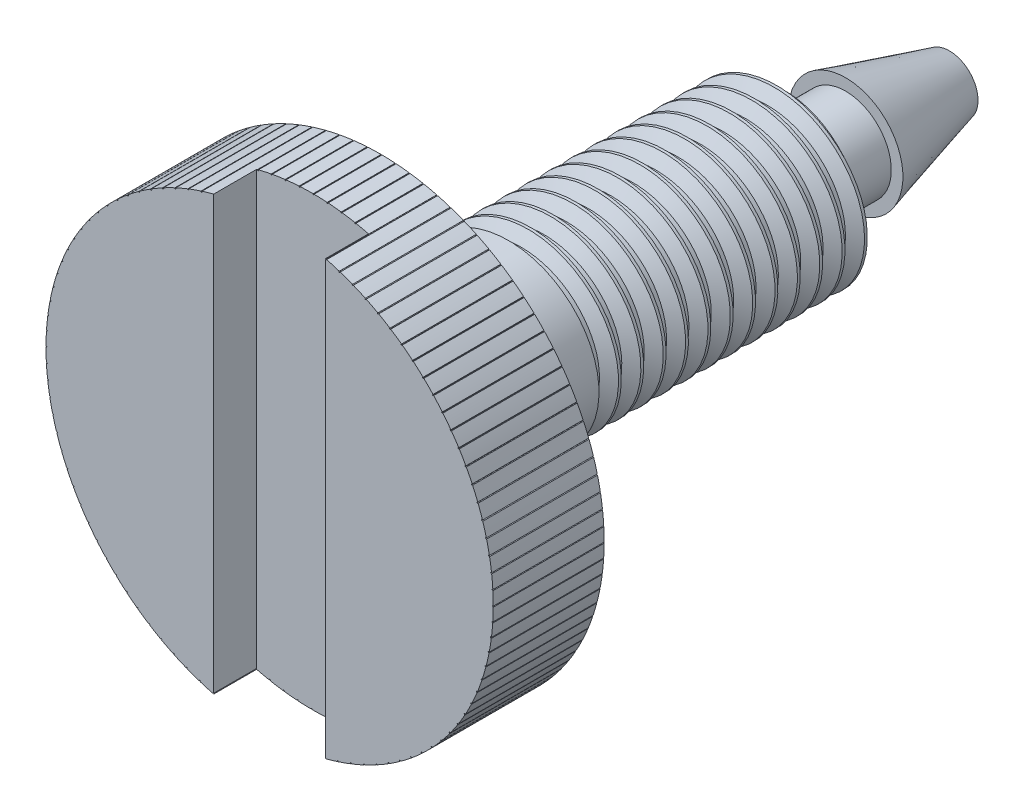
SolidWorks part; units mm, degrees
other "Markup1"
sketch "Sketch10" plane through (-3.175, 3.175, -9.652) normal (-0.9356, 0.3399, -0.0956) x (0.0407, 0.3726, 0.9271)
material "Brass"
ref_plane "Front Plane" through (0, 0, 0) normal (0, 0, 1) x (1, 0, 0)
ref_plane "Top Plane" through (0, 0, 0) normal (0, 1, 0) x (1, 0, 0)
ref_plane "Right Plane" through (0, 0, 0) normal (1, 0, 0) x (0, 0, -1)
sketch "Sketch1" plane through (0, 0, 0) normal (0, 1, 0) x (1, 0, 0)
  line L0 (0, 0) -> (3.175, 0)
  line L1 (3.175, 0) -> (3.175, 1.5748)
  line L2 (3.175, 1.5748) -> (1.2573, 1.5748)
  line L3 (1.2573, 1.5748) -> (1.2573, 7.3152)
  line L4 (1.2573, 7.3152) -> (0.6477, 7.3152)
  line L7 (0, 9.652) -> (0, 0) construction
  line L8 (0, 0) -> (0, 9.652)
  line L10 (0.6477, 7.3152) -> (0.6477, 8.1788)
  line L13 (0.6477, 8.1788) -> (0.8128, 8.1788)
  line L14 (0.8128, 8.1788) -> (0.4064, 9.652)
  line L15 (0, 9.652) -> (0.4064, 9.652)
  dimension "D1" = 3.175
  dimension "D2" = 0.6096
  dimension "D3" = 0.4064
  dimension "D4" = 9.652
  dimension "D5" = 1.5748
  dimension "D6" = 1.2573
  dimension "D7" = 5.7404
  dimension "D8" = 0.8636
  dimension "D9" = 0.1651
revolve "Revolve1" add sketch "Sketch1" angle 360 about L7
cosmetic thread "Cosmetic Thread2" parameters "D2"=1.1455
sketch "Sketch2" plane through (0, 0, 0) normal (0, 1, 0) x (1, 0, 0)
  line L1 (-0.7937, -0.6096) -> (0.7938, -0.6096)
  line L2 (-0.7937, -0.6096) -> (-0.7937, 0.6096)
  line L3 (-0.7937, 0.6096) -> (0.7938, 0.6096)
  line L4 (0.7938, -0.6096) -> (0.7938, 0.6096)
  line L5 (-0.7937, -0.6096) -> (0.7938, 0.6096) construction
  line L6 (-0.7937, 0.6096) -> (0.7938, -0.6096) construction
  point P0 (0, 0)
  dimension "D1" = 1.5875
  dimension "D2" = 1.2192
extrude "Cut-Extrude1" cut sketch "Sketch2" against normal mid plane 12.7
thread "Thread1" pitch 0.3175 method cut profile "Thread Profile1" start angle 0, offset 0.508, length 4.318, pitch 0.3175, diameter 2.5146
cosmetic thread "Cosmetic Thread1" parameters "D2"=1.5146
cosmetic thread "Cosmetic Thread3" parameters "D2"=1.1455
cosmetic thread "Cosmetic Thread4" parameters "D2"=1.1455
ref_plane "Plane1" through (1.2573, 0, -7.8232) normal (0, -1, 0) x (1, 0, 0)
sketch "Thread Profile1" plane through (1.2573, 0, -7.8232) normal (0, -1, 0) x (1, 0, 0)
  line L0 (0, 0) -> (0, 0.3175) construction
  line L11 (0, 0) -> (0, 0.2778)
  line L12 (0, 0.2778) -> (-0.1719, 0.1786)
  line L13 (-0.1719, 0.1786) -> (-0.1719, 0.0992)
  line L15 (-0.1719, 0.0992) -> (0, 0)
  line L17 (-0.1719, 0.1389) -> (0, 0.1389) construction
  point P2 (0, 0)
  dimension "Pitch" = 0.3175
  dimension "Profile_Angle" = 60
  dimension "Profile_Land" = 0.0794
  dimension "Profile_Height" = 0.1719
sketch "Sketch9" plane through (0, 0, -1.5748) normal (0, 0, -1) x (-1, 0, 0)
  line L1 (-2.9446, 1.1491) -> (-2.9604, 1.1491)
  line L2 (-2.9446, 1.1491) -> (-2.9446, 1.1612)
  line L3 (-2.9446, 1.1612) -> (-2.9604, 1.1612)
  line L4 (-2.9604, 1.1491) -> (-2.9604, 1.1612)
extrude "Cut-Extrude4" cut sketch "Sketch9" against normal through all
pattern_circular "CirPattern1" count 100 over 360 about axis through (0, 0, -9.652) along (0, 0, -1) of "Cut-Extrude4"
